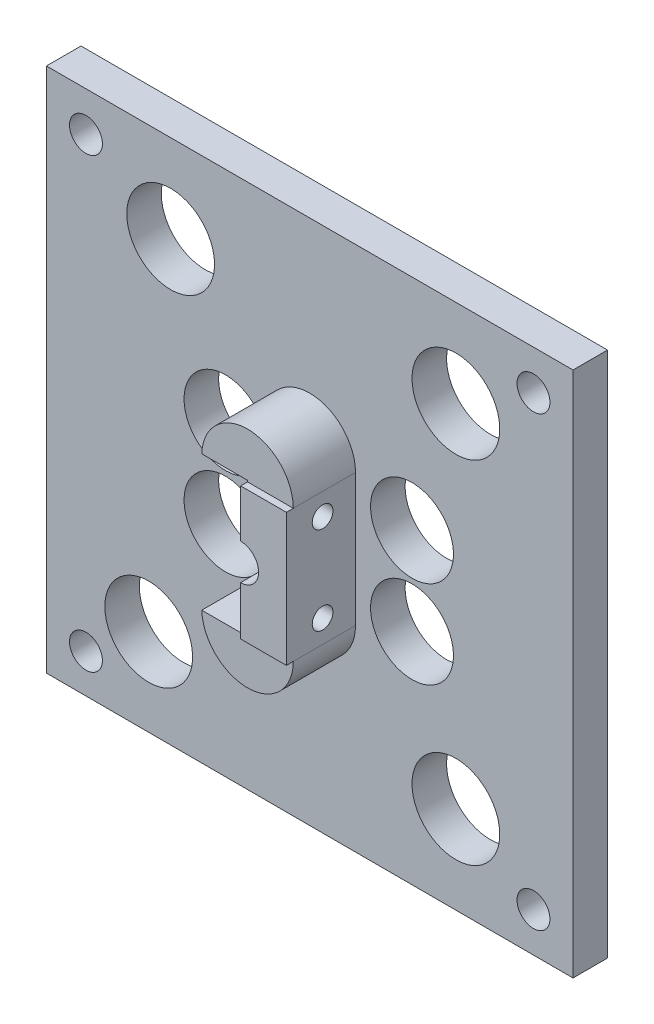
SolidWorks part; units mm, degrees
material "Pure Gold"
ref_plane "Front" through (0, 0, 0) normal (0, 0, 1) x (1, 0, 0)
ref_plane "Top" through (0, 0, 0) normal (0, 1, 0) x (1, 0, 0)
ref_plane "Right" through (0, 0, 0) normal (1, 0, 0) x (0, 0, -1)
sketch "Sketch4" plane through (0, 0, 0) normal (0, 0, 1) x (1, 0, 0)
  line L0 (0, -42.8625) -> (0, 41.275) construction
  line L1 (-49.15, -15.5) -> (-80.15, 15.5) construction
  line L2 (-80.15, -15.5) -> (-49.15, 15.5) construction
  line L3 (-39.925, 44.5615) -> (-39.925, -66.5635) construction
  line L4 (-71.275, 44.5615) -> (-71.275, -66.5635) construction
  line L8 (-62.05, 15.5) -> (-31.05, -15.5) construction
  line L9 (-31.05, 15.5) -> (-62.05, -15.5) construction
  line L11 (-31.05, 36.624) -> (-31.05, -53.8635) construction
  line L12 (43.75, 0) -> (-164.4633, 0) construction
  line L13 (-62.05, 36.624) -> (-62.05, -53.8635) construction
  line L14 (-49.15, 36.624) -> (-49.15, -53.8635) construction
  line L15 (-80.15, 36.624) -> (-80.15, -53.8635) construction
  line L16 (-113.2228, 15.5) -> (-0.2036, 15.5) construction
  line L17 (-113.2228, -15.5) -> (-0.2036, -15.5) construction
  line L18 (-25, -66.5635) -> (-25, 44.5615) construction
  line L19 (-68.1, -66.5635) -> (-68.1, 44.5615) construction
  line L20 (-43.1, 44.5615) -> (-43.1, -66.5635) construction
  line L21 (-86.2, -66.5635) -> (-86.2, 44.5615) construction
  line L22 (5.8397, -21.55) -> (-134.1626, -21.55) construction
  line L23 (5.8397, 21.55) -> (-134.1626, 21.55) construction
  line L24 (10.9249, -24.725) -> (-138.6228, -24.725) construction
  line L25 (10.9249, 24.725) -> (-138.6228, 24.725) construction
  line L26 (-89.375, 44.5615) -> (-89.375, -66.5635) construction
  line L27 (-21.825, 44.5615) -> (-21.825, -66.5635) construction
  circle A0 centre (0, 0) radius 12.7 construction
  circle A1 centre (0, 0) radius 15.875 construction
  circle A2 centre (0, 0) radius 9.46 construction
  circle A3 centre (-93.65, 0) radius 9.46 construction
  arc A4 (-93.65, 12.7) -> (-93.65, -12.7) centre (-93.65, 0) ccw construction
  circle A5 centre (27.27, 0) radius 9.46 construction
  circle A6 centre (27.27, 0) radius 12.7 construction
  circle A7 centre (-120.3675, 0) radius 9.46 construction
  circle A8 centre (-120.3675, 0) radius 12.7 construction
  point P3 (0, 0)
  point P6 (-49.15, -15.5)
  point P11 (-93.65, 0)
  point P12 (-49.15, 15.5)
  point P13 (-46.55, 0)
  point P14 (-80.15, 15.5)
  point P15 (-80.15, -15.5)
  point P61 (-64.65, 0)
  point P65 (27.27, 0)
  point P66 (-120.3675, 0)
  dimension "D20" = 3.175
  dimension "D18" = 29
  dimension "D26" = 73.82
  dimension "D27" = 64.65
  dimension "D2" = 31
  dimension "D3" = 25
  dimension "D4" = 31
  dimension "D5" = 21.825
  dimension "D6" = 15.5
  dimension "D7" = 15.5
  dimension "D8" = 6.05
  dimension "D9" = 6.05
  dimension "D10" = 6.05
  dimension "D11" = 6.05
  dimension "D12" = 6.05
  dimension "D13" = 6.05
  dimension "D14" = 3.175
  dimension "D15" = 3.175
  dimension "D16" = 3.175
  dimension "D17" = 3.175
  dimension "D19" = 3.175
  dimension "D21" = 3.175
  dimension "D22" = 46.55
  dimension "D23" = 47.1
  dimension "D24" = 58.32
  dimension "D25" = 147.6375
sketch "Sketch5" plane through (0, 0, 0) normal (0, 0, 1) x (1, 0, 0)
  line L0 (-46.55, 1.6) -> (-46.55, -2.6) construction
  line L4 (-46.55, -2.6) -> (-46.55, -9.6636)
  line L5 (-46.55, 9.525) -> (-39.925, 9.525)
  line L7 (-39.925, 44.5615) -> (-39.925, -66.5635) construction
  line L8 (-39.925, -9.6636) -> (-39.925, 9.525)
  line L9 (-46.55, -9.6636) -> (-39.925, -9.6636)
  line L13 (-46.55, 9.525) -> (-46.55, 2.6)
  circle A0 centre (-46.55, 0) radius 2.6 construction
  arc A1 (-46.55, 2.6) -> (-46.55, -2.6) centre (-46.55, 0) cw
extrude "Extrude1" add sketch "Sketch5" along normal blind 10
sketch "Sketch7" plane through (-39.925, 0, 0) normal (1, 0, 0) x (0, 0, -1)
  line L0 (0, -9.6636) -> (0, 9.525) construction
  circle A0 centre (-4.7625, 6.35) radius 1.5
  circle A1 centre (-4.7625, -6.35) radius 1.5
  dimension "D1" = 4.7625
extrude "Extrude3" cut sketch "Sketch7" against normal up to surface (6.625 mm away) up to face at (-46.55, 6.0625, 5)
sketch "Sketch6" plane through (0, 0, 0) normal (0, 0, -1) x (-1, 0, 0)
  line L0 (14.17, 50.8) -> (14.17, -98.425) construction
  line L1 (78.93, 63.5) -> (78.93, -95.3388) construction
  line L2 (84.65, 61.9125) -> (84.65, -95.25) construction
  line L3 (8.45, 55.5625) -> (8.45, -109.5375) construction
  line L4 (125.4125, 32.38) -> (-41.8258, 32.38) construction
  line L5 (123.825, 38.1) -> (-50.9969, 38.1) construction
  line L6 (119.0625, -38.1) -> (-36.5125, -38.1) construction
  line L7 (119.0625, -32.38) -> (-42.8625, -32.38) construction
  line L9 (84.65, 38.1) -> (8.45, 38.1)
  line L10 (84.65, 38.1) -> (84.65, -37.9954)
  line L11 (84.65, -37.9954) -> (8.45, -38.1)
  line L12 (8.45, 38.1) -> (8.45, -38.1)
  circle A0 centre (78.93, -32.38) radius 2.3813
  circle A1 centre (14.17, -32.38) radius 2.3812
  circle A2 centre (14.17, 32.38) radius 2.3812
  circle A3 centre (78.93, 32.38) radius 2.3813
  circle A4 centre (46.55, 0) radius 2.6
  circle A5 centre (69.85, -25.4) radius 6.35
  circle A6 centre (66.675, 25.4) radius 6.35
  circle A7 centre (25.4, 25.4) radius 6.35
  circle A8 centre (25.4, -25.4) radius 6.35
  circle A9 centre (58.7375, -6.35) radius 6
  circle A10 centre (58.7375, 6.35) radius 6
  circle A11 centre (31.75, -6.35) radius 6
  circle A12 centre (31.75, 6.35) radius 6
  dimension "D1" = 38.1
  dimension "D2" = 5.72
  dimension "D3" = 38.1
  dimension "D4" = 5.72
  dimension "D5" = 38.1
  dimension "D6" = 38.1
  dimension "D7" = 5.72
  dimension "D8" = 5.72
extrude "Extrude2" add sketch "Sketch6" along normal blind 5
sketch "Sketch9" plane through (0, 0, 0) normal (0, 0, 1) x (1, 0, 0)
  line L0 (-53.175, -9.6636) -> (-39.925, -9.6636)
  line L1 (-39.925, 9.525) -> (-53.175, 9.525)
  arc A0 (-39.925, -9.6636) -> (-53.175, -9.6636) centre (-46.55, -9.6636) cw
  arc A1 (-39.925, 9.525) -> (-53.175, 9.525) centre (-46.55, 9.525) ccw
extrude "Extrude4" add sketch "Sketch9" along normal blind 9
sketch "Sketch10" plane through (0, 0, 9) normal (0, 0, 1) x (1, 0, 0)
  line L0 (-46.55, 9.525) -> (-46.55, 9.725)
  line L1 (-46.55, -9.6636) -> (-46.55, -9.8636)
  line L2 (-46.55, -9.8636) -> (-53.9976, -9.8636)
  line L3 (-53.9976, -9.8636) -> (-53.9976, 9.725)
  line L4 (-53.9976, 9.725) -> (-46.55, 9.725)
  line L5 (-46.55, -9.6636) -> (-46.55, 9.525)
extrude "Extrude5" cut sketch "Sketch10" against normal blind 9
